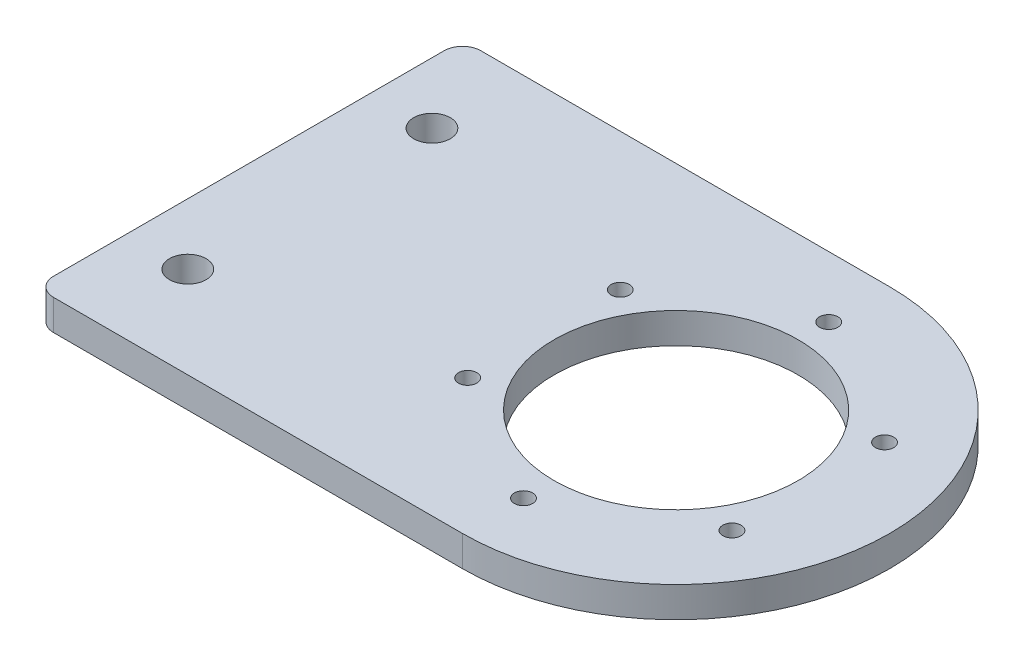
SolidWorks part; units mm, degrees
ref_plane "Front Plane" through (0, 0, 0) normal (0, 0, 1) x (1, 0, 0)
ref_plane "Top Plane" through (0, 0, 0) normal (0, 1, 0) x (1, 0, 0)
ref_plane "Right Plane" through (0, 0, 0) normal (1, 0, 0) x (0, 0, -1)
sketch "Sketch1" plane through (0, 0, 0) normal (0, 1, 0) x (1, 0, 0)
  line L0 (-70, 35) -> (0, 35)
  line L1 (0, -35) -> (-70, -35)
  line L2 (-70, -35) -> (-70, 35)
  line L3 (-60, 20) -> (-60, -20) construction
  line L4 (-87.1616, 0) -> (54.6948, 0) construction
  circle A0 centre (0, 0) radius 25 construction
  arc A1 (0, 35) -> (0, -35) centre (0, 0) cw
  circle A2 centre (0, 25) radius 1.5
  circle A3 centre (21.6506, 12.5) radius 1.5
  circle A4 centre (21.6506, -12.5) radius 1.5
  circle A5 centre (0, -25) radius 1.5
  circle A6 centre (-21.6506, -12.5) radius 1.5
  circle A7 centre (-21.6506, 12.5) radius 1.5
  circle A8 centre (-60, 20) radius 3
  circle A9 centre (-60, -20) radius 3
  circle A10 centre (0, 0) radius 20
  point P23 (0, 0)
  point P27 (-60, 0)
  dimension "D3" = 50
  dimension "D4" = 3
  dimension "D8" = 6
  dimension "D9" = 40
  dimension "D1" = 70
  dimension "D2" = 70
  dimension "D6" = 40
  dimension "D7" = 10
  dimension "D5" = 6
extrude "Boss-Extrude1" add sketch "Sketch1" along normal blind 5
fillet "Fillet1" radius 3 2 edges at (-70, 2.5, 35) (-70, 2.5, -35)
